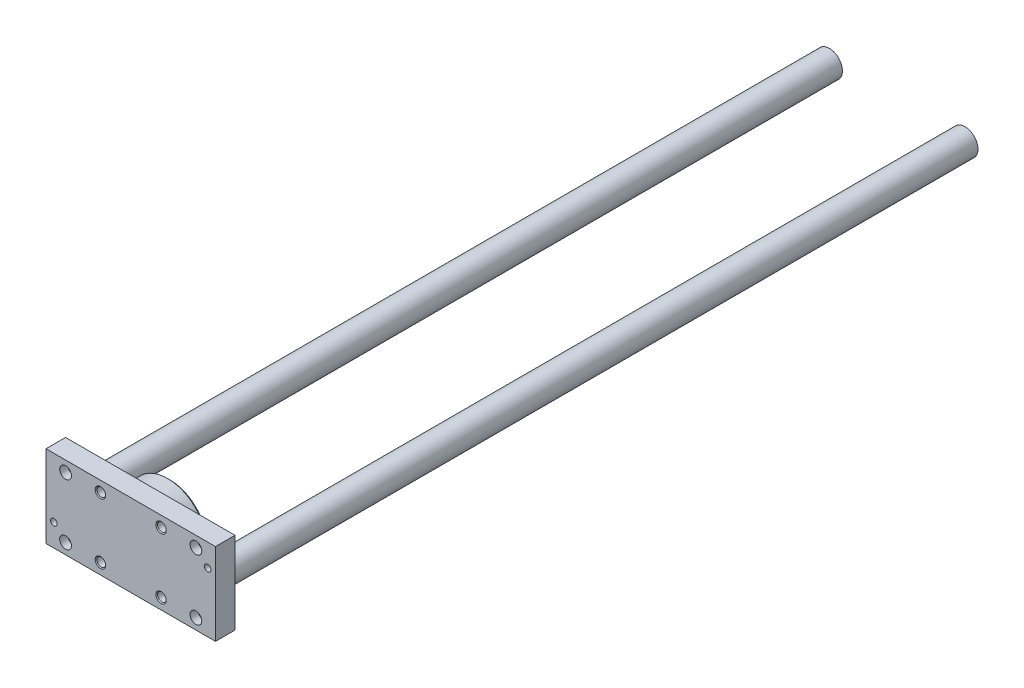
SolidWorks part; units mm, degrees
ref_plane "Front Plane" through (0, 0, 0) normal (0, 0, 1) x (1, 0, 0)
ref_plane "Top Plane" through (0, 0, 0) normal (0, 1, 0) x (1, 0, 0)
ref_plane "Right Plane" through (0, 0, 0) normal (1, 0, 0) x (0, 0, -1)
ref_plane "Plane1" through (0, 0, 89) normal (0, 0, 1) x (1, 0, 0)
sketch "Sketch1" plane through (0, 0, 89) normal (0, 0, 1) x (1, 0, 0)
  line L0 (-65, 31.5) -> (-65, -31.5)
  line L1 (-65, -31.5) -> (65, -31.5)
  line L2 (65, -31.5) -> (65, 31.5)
  line L3 (65, 31.5) -> (-65, 31.5)
extrude "Boss-Extrude1" add sketch "Sketch1" against normal blind 15
ref_plane "Plane2" through (23.25, 0, 0) normal (1, 0, 0) x (0, 0, -1)
sketch "Sketch2" plane through (23.25, 0, 0) normal (1, 0, 0) x (0, 0, -1)
  line L0 (-89, 23.25) -> (-89, 27.25)
  line L1 (-89, 27.25) -> (-88.3235, 26.5735)
  line L2 (-88.3235, 26.5735) -> (-74.6765, 26.5735)
  line L3 (-74.6765, 26.5735) -> (-74, 27.25)
  line L4 (-74, 27.25) -> (-74, 23.25)
  line L5 (-74, 23.25) -> (-89, 23.25)
  line L6 (-74, 23.25) -> (-89, 23.25) construction
revolve "Cut-Revolve1" cut sketch "Sketch2" angle 360 about L6
cosmetic thread "Cosmetic Thread1" parameters "D1"=15, "D2"=8
sketch "Sketch3" plane through (0, 0, 89) normal (0, 0, 1) x (1, 0, 0)
  line L0 (23.25, 23.25) -> (-23.25, 23.25)
  line L1 (23.25, 23.25) -> (23.25, -23.25)
pattern_linear "LPattern1" count 2 spacing 46.5 along (-1, 0, 0) count 2 spacing 46.5 along (0, -1, 0) of "Cut-Revolve1"
cosmetic thread "Cosmetic Thread2" parameters "D1"=15, "D2"=8
cosmetic thread "Cosmetic Thread3" parameters "D1"=15, "D2"=8
cosmetic thread "Cosmetic Thread4" parameters "D1"=15, "D2"=8
ref_plane "Plane3" through (50, 0, 0) normal (1, 0, 0) x (0, 0, -1)
sketch "Sketch4" plane through (50, 0, 0) normal (1, 0, 0) x (0, 0, -1)
  line L0 (-89, 23.25) -> (-89, 27.75)
  line L1 (-89, 27.75) -> (-83, 27.75)
  line L2 (-83, 27.75) -> (-83, 30.75)
  line L3 (-83, 30.75) -> (-74, 30.75)
  line L4 (-74, 30.75) -> (-74, 23.25)
  line L5 (-74, 23.25) -> (-89, 23.25)
  line L6 (-74, 23.25) -> (-89, 23.25) construction
revolve "Cut-Revolve2" cut sketch "Sketch4" angle 360 about L6
sketch "Sketch5" plane through (0, 0, 89) normal (0, 0, 1) x (1, 0, 0)
  line L0 (50, 23.25) -> (-50, 23.25)
  line L1 (50, 23.25) -> (50, -23.25)
pattern_linear "LPattern2" count 2 spacing 100 along (-1, 0, 0) count 2 spacing 46.5 along (0, -1, 0) of "Cut-Revolve2"
sketch "Sketch6" plane through (0, 0, 89) normal (0, 0, 1) x (1, 0, 0)
  circle A0 centre (-52, 0) radius 10
extrude "Boss-Extrude2" add sketch "Sketch6" against normal blind 588
sketch "Sketch7" plane through (0, 0, 89) normal (0, 0, 1) x (1, 0, 0)
  circle A0 centre (52, 0) radius 10
extrude "Boss-Extrude3" add sketch "Sketch7" against normal blind 588
ref_plane "Plane4" through (0, 0, 0) normal (0, 0, 1) x (1, 0, 0)
sketch "Sketch8" plane through (0, 0, 0) normal (1, 0, 0) x (0, 0, -1)
  line L0 (-74, 0) -> (-74, 30)
  line L1 (-74, 30) -> (-60.6, 30)
  line L2 (-60.6, 30) -> (-59, 28.4)
  line L3 (-59, 28.4) -> (-59, 11)
  line L4 (-59, 11) -> (-50, 11)
  line L5 (-50, 11) -> (-49, 10)
  line L6 (-49, 10) -> (-49, 0)
  line L7 (-49, 0) -> (-74, 0)
  line L8 (-49, 0) -> (-74, 0) construction
revolve "Revolve1" add sketch "Sketch8" angle 360 about L8
sketch "Sketch9" plane through (0, 0, 0) normal (1, 0, 0) x (0, 0, -1)
  line L0 (-74, 0) -> (-74, 7.188)
  line L1 (-74, 7.188) -> (-49.812, 7.188)
  line L2 (-49.812, 7.188) -> (-49, 8)
  line L3 (-49, 8) -> (-49, 0)
  line L4 (-49, 0) -> (-74, 0)
  line L5 (-49, 0) -> (-74, 0) construction
revolve "Cut-Revolve3" cut sketch "Sketch9" angle 360 about L5
cosmetic thread "Cosmetic Thread5" parameters "D1"=25, "D2"=16
ref_plane "Plane5" through (0, 0, 54) normal (0, 0, 1) x (1, 0, 0)
ref_plane "Plane6" through (0, 0, 52) normal (0, 0, 1) x (1, 0, 0)
ref_plane "Plane7" through (0, 0, 49) normal (0, 0, 1) x (1, 0, 0)
sketch "Sketch10" plane through (0, 0, 49) normal (0, 0, 1) x (1, 0, 0)
  line L0 (-20, -20) -> (20, -20)
  line L1 (20, -20) -> (20, 20)
  line L2 (20, 20) -> (-20, 20)
  line L3 (-20, 20) -> (-20, -20)
  line L4 (-9, -15) -> (9, -15)
  line L5 (9, -15) -> (9, 15)
  line L6 (9, 15) -> (-9, 15)
  line L7 (-9, 15) -> (-9, -15)
extrude "Cut-Extrude1" cut sketch "Sketch10" along normal blind 10
ref_plane "Plane8" through (0, 0, 42) normal (0, 0, 1) x (1, 0, 0)
ref_plane "FUEHRUNG XY" through (0, 0, 0) normal (0, 0, 1) x (1, 0, 0)
ref_plane "FUEHRUNG XZ" through (0, 0, 0) normal (0, -1, 0) x (-1, 0, 0)
ref_plane "FUEHRUNG YZ" through (0, 0, 0) normal (1, 0, 0) x (0, 0, -1)
ref_axis "FUEHRUNG X" through (-80.9, 0, 0) along (1, 0, 0)
ref_axis "FUEHRUNG Y" through (0, -50, 0) along (0, 1, 0)
ref_axis "FUEHRUNG Z" through (0, 0, 80.9) along (0, 0, -1)
sketch3d "FUEHRUNG"
  point P0 (0, 0, 0)
sketch "Sketch11" plane through (0, 0, 74) normal (0, 0, -1) x (-1, 0, 0)
  circle A0 centre (-59, 14.25) radius 2.5
  circle A1 centre (59, -14.25) radius 2.5
  circle A2 centre (-50, 23.25) radius 4.5 construction
  circle A3 centre (-50, 23.25) radius 7.5 construction
  circle A4 centre (50, -23.25) radius 4.5 construction
  dimension "D2" = 9
  dimension "D4" = 9
  dimension "D5" = 5
  dimension "D6" = 5
  dimension "D1" = 9
  dimension "D3" = 9
extrude "Cut-Extrude2" cut sketch "Sketch11" against normal through all
other "Freeze***"
